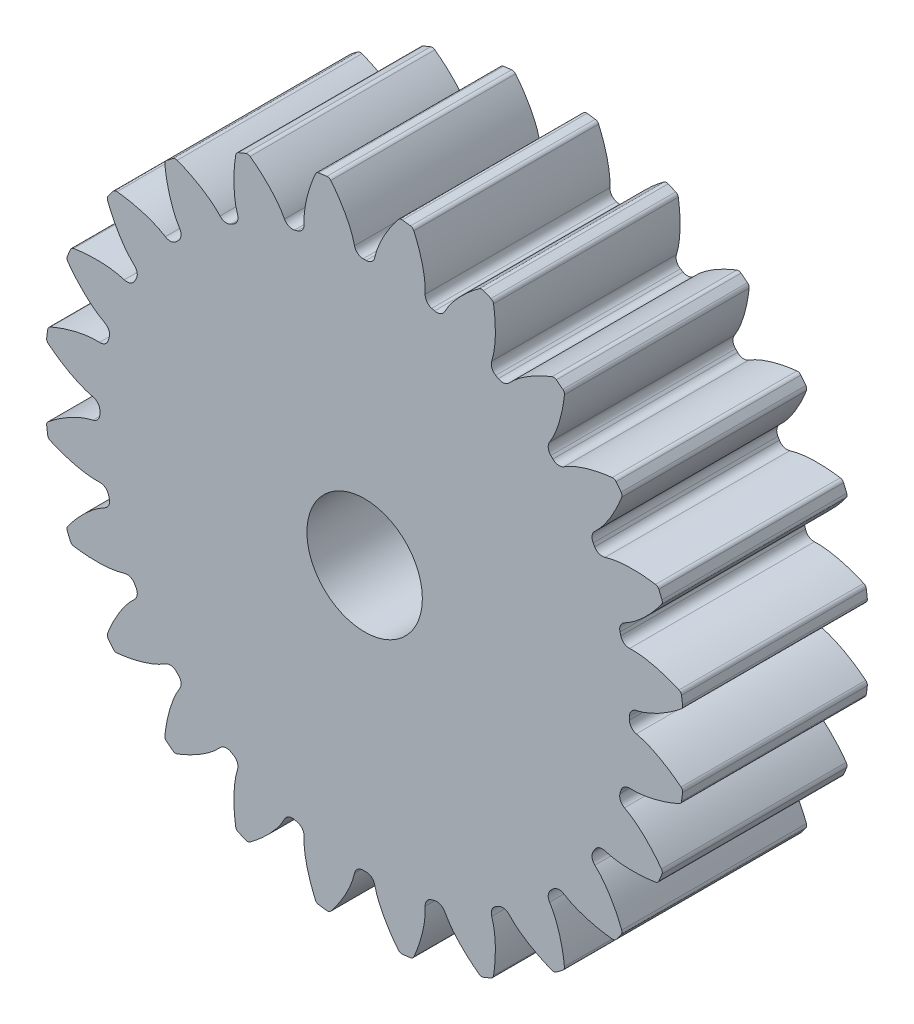
SolidWorks part; units mm, degrees
material "DELRIN"
ref_plane "Front" through (0, 0, 0) normal (0, 0, 1) x (1, 0, 0)
ref_plane "Top" through (0, 0, 0) normal (0, 1, 0) x (1, 0, 0)
ref_plane "Right" through (0, 0, 0) normal (1, 0, 0) x (0, 0, -1)
sketch "Sketch1" plane through (0, 0, 0) normal (0, 0, 1) x (1, 0, 0)
  circle A0 centre (0, 0) radius 22.0133
  dimension "OutsideDiameter" = 44.0267
extrude "Boss-Extrude1" add sketch "Sketch1" along normal blind 12.7
sketch "Sketch3" plane through (0, 0, 0) normal (0, 0, 1) x (1, 0, 0)
  line L0 (0, 0) -> (43.7181, 0) construction
  line L2 (0, 0) -> (-0.6456, 18.1919) construction
  line L3 (0, 0) -> (0.6456, 18.1919) construction
  line L4 (0.6456, 18.1919) -> (0.6532, 18.4046) construction
  line L5 (0, 0) -> (0, 61.276) construction
  line L6 (-0.6456, 18.1919) -> (-0.6532, 18.4046) construction
  circle A0 centre (0, 0) radius 22.0133 construction
  circle A1 centre (0, 0) radius 20.32 construction
  circle A2 centre (0, 0) radius 18.4162 construction
  arc A3 (0.6456, 18.1919) -> (-0.6456, 18.1919) centre (0, 0) ccw construction
  arc A5 (2.4284, 21.879) -> (-2.4284, 21.879) centre (0, 0) ccw
  spline S0 degree 4 poles (-0.6532, 18.4046) (-0.6535, 18.4104) (-0.6545, 18.4268) (-0.6575, 18.4576) (-0.6638, 18.5078) (-0.6738, 18.5716) (-0.6892, 18.6539) (-0.7103, 18.7504) (-0.7366, 18.856) (-0.7687, 18.9703) (-0.8037, 19.0839) (-0.8414, 19.1967) (-0.8815, 19.3085) (-0.9329, 19.4434) (-0.9987, 19.6042) (-1.0815, 19.7907) (-1.1824, 20.0005) (-1.2926, 20.2122) (-1.4071, 20.4189) (-1.5297, 20.6255) (-1.6532, 20.8239) (-1.7884, 21.0275) (-1.9168, 21.2143) (-2.0682, 21.4208) (-2.1926, 21.5866) (-2.3648, 21.8022) (-2.4689, 21.9286) (-2.5935, 22.0754) (-2.6502, 22.14) (-2.6851, 22.1798) knots 0 0 0 0 0 0.005377 0.015084 0.028532 0.04661 0.064855 0.092111 0.119476 0.146842 0.174209 0.201575 0.228941 0.256307 0.307035 0.361767 0.4165 0.471232 0.525964 0.580697 0.635429 0.690161 0.744894 0.799626 0.854358 0.909091 0.954545 1 1 1 1 1 construction
  spline S1 degree 4 poles (-0.6532, 18.4046) (-0.6535, 18.4104) (-0.6545, 18.4268) (-0.6575, 18.4576) (-0.6638, 18.5078) (-0.6738, 18.5716) (-0.6892, 18.6539) (-0.7103, 18.7504) (-0.7366, 18.856) (-0.7687, 18.9703) (-0.8037, 19.0839) (-0.8414, 19.1967) (-0.8815, 19.3085) (-0.9329, 19.4434) (-0.9987, 19.6042) (-1.0815, 19.7907) (-1.1824, 20.0005) (-1.2926, 20.2122) (-1.4071, 20.4189) (-1.5297, 20.6255) (-1.6532, 20.8239) (-1.7884, 21.0275) (-1.9168, 21.2143) (-2.0682, 21.4208) (-2.1926, 21.5866) (-2.3275, 21.7555) (-2.394, 21.8373) (-2.4284, 21.879) knots 0 0 0 0 0 0.005377 0.015084 0.028532 0.04661 0.064855 0.092111 0.119476 0.146842 0.174209 0.201575 0.228941 0.256307 0.307035 0.361767 0.4165 0.471232 0.525964 0.580697 0.635429 0.690161 0.744894 0.799626 0.854358 0.909091 0.909091 0.909091 0.909091 0.909091
  spline S2 degree 4 poles (0.6532, 18.4046) (0.6535, 18.4104) (0.6545, 18.4268) (0.6575, 18.4576) (0.6638, 18.5078) (0.6738, 18.5716) (0.6892, 18.6539) (0.7103, 18.7504) (0.7366, 18.856) (0.7687, 18.9703) (0.8037, 19.0839) (0.8414, 19.1967) (0.8815, 19.3085) (0.9329, 19.4434) (0.9987, 19.6042) (1.0815, 19.7907) (1.1824, 20.0005) (1.2926, 20.2122) (1.4071, 20.4189) (1.5297, 20.6255) (1.6532, 20.8239) (1.7884, 21.0275) (1.9168, 21.2143) (2.0682, 21.4208) (2.1926, 21.5866) (2.3648, 21.8022) (2.4689, 21.9286) (2.5935, 22.0754) (2.6502, 22.14) (2.6851, 22.1798) knots 0 0 0 0 0 0.005377 0.015084 0.028532 0.04661 0.064855 0.092111 0.119476 0.146842 0.174209 0.201575 0.228941 0.256307 0.307035 0.361767 0.4165 0.471232 0.525964 0.580697 0.635429 0.690161 0.744894 0.799626 0.854358 0.909091 0.954545 1 1 1 1 1 construction
  spline S3 degree 4 poles (0.6532, 18.4046) (0.6535, 18.4104) (0.6545, 18.4268) (0.6575, 18.4576) (0.6638, 18.5078) (0.6738, 18.5716) (0.6892, 18.6539) (0.7103, 18.7504) (0.7366, 18.856) (0.7687, 18.9703) (0.8037, 19.0839) (0.8414, 19.1967) (0.8815, 19.3085) (0.9329, 19.4434) (0.9987, 19.6042) (1.0815, 19.7907) (1.1824, 20.0005) (1.2926, 20.2122) (1.4071, 20.4189) (1.5297, 20.6255) (1.6532, 20.8239) (1.7884, 21.0275) (1.9168, 21.2143) (2.0682, 21.4208) (2.1926, 21.5866) (2.3275, 21.7555) (2.394, 21.8373) (2.4284, 21.879) knots 0 0 0 0 0 0.005377 0.015084 0.028532 0.04661 0.064855 0.092111 0.119476 0.146842 0.174209 0.201575 0.228941 0.256307 0.307035 0.361767 0.4165 0.471232 0.525964 0.580697 0.635429 0.690161 0.744894 0.799626 0.854358 0.909091 0.909091 0.909091 0.909091 0.909091
  point P0 (0, 18.2033)
  dimension "OutsideDiameter" = 44.0267
  dimension "PitchCircle" = 40.64
  dimension "BaseCircle" = 36.8323
  dimension "DedendumCircle" = 36.4067
sketch "DCLTBC" plane through (0, 0, 0) normal (0, 0, 1) x (1, 0, 0)
  line L0 (0, 0) -> (41.04, 0) construction
  line L1 (-0.6456, 18.1919) -> (-0.6532, 18.4046) construction
  line L2 (0.6456, 18.1919) -> (0.6532, 18.4046) construction
  line L3 (-0.6456, 18.1919) -> (-0.6532, 18.4046)
  line L4 (0.6456, 18.1919) -> (0.6532, 18.4046)
  line L5 (0, 0) -> (0, 104.9356) construction
  circle A0 centre (0, 0) radius 22.0133
  circle A1 centre (0, 0) radius 20.32 construction
  circle A2 centre (0, 0) radius 18.4162 construction
  arc A3 (0.6456, 18.1919) -> (-0.6456, 18.1919) centre (0, 0) ccw construction
  arc A4 (0.6456, 18.1919) -> (-0.6456, 18.1919) centre (0, 0) ccw
  spline S0 degree 4 poles (-999.1981, -34.6963) (-14.3386, 16.1827) (-0.8334, 17.2583) (-0.5869, 17.8923) (-0.6638, 18.5078) (-0.6738, 18.5716) (-0.6892, 18.6539) (-0.7103, 18.7504) (-0.7366, 18.856) (-0.7687, 18.9703) (-0.8037, 19.0839) (-0.8414, 19.1967) (-0.8815, 19.3085) (-0.9329, 19.4434) (-0.9987, 19.6042) (-1.0815, 19.7907) (-1.1824, 20.0005) (-1.2926, 20.2122) (-1.4071, 20.4189) (-1.5297, 20.6255) (-1.6532, 20.8239) (-1.7884, 21.0275) (-1.9168, 21.2143) (-2.0682, 21.4208) (-2.6456, 22.1903) (-4.6145, 24.4426) (15.9918, -0.7638) (-639.5408, 792.6401) knots -0.524597 -0.524597 -0.524597 -0.524597 -0.524597 0.005377 0.015084 0.028532 0.04661 0.064855 0.092111 0.119476 0.146842 0.174209 0.201575 0.228941 0.256307 0.307035 0.361767 0.4165 0.471232 0.525964 0.580697 0.635429 0.690161 0.744894 0.799626 0.854358 1.706051 1.706051 1.706051 1.706051 1.706051 only from (-0.6532, 18.4046) to (-2.4284, 21.879) construction
  spline S1 degree 4 poles (999.1981, -34.6963) (14.3386, 16.1827) (0.8334, 17.2583) (0.5869, 17.8923) (0.6638, 18.5078) (0.6738, 18.5716) (0.6892, 18.6539) (0.7103, 18.7504) (0.7366, 18.856) (0.7687, 18.9703) (0.8037, 19.0839) (0.8414, 19.1967) (0.8815, 19.3085) (0.9329, 19.4434) (0.9987, 19.6042) (1.0815, 19.7907) (1.1824, 20.0005) (1.2926, 20.2122) (1.4071, 20.4189) (1.5297, 20.6255) (1.6532, 20.8239) (1.7884, 21.0275) (1.9168, 21.2143) (2.0682, 21.4208) (2.6456, 22.1903) (4.6145, 24.4426) (-15.9918, -0.7638) (639.5408, 792.6401) knots -0.524597 -0.524597 -0.524597 -0.524597 -0.524597 0.005377 0.015084 0.028532 0.04661 0.064855 0.092111 0.119476 0.146842 0.174209 0.201575 0.228941 0.256307 0.307035 0.361767 0.4165 0.471232 0.525964 0.580697 0.635429 0.690161 0.744894 0.799626 0.854358 1.706051 1.706051 1.706051 1.706051 1.706051 only from (0.6532, 18.4046) to (2.4284, 21.879) construction
  spline S2 degree 4 poles (-0.6532, 18.4046) (-0.6535, 18.4104) (-0.6545, 18.4268) (-0.6575, 18.4576) (-0.6638, 18.5078) (-0.6738, 18.5716) (-0.6892, 18.6539) (-0.7103, 18.7504) (-0.7366, 18.856) (-0.7687, 18.9703) (-0.8037, 19.0839) (-0.8414, 19.1967) (-0.8815, 19.3085) (-0.9329, 19.4434) (-0.9987, 19.6042) (-1.0815, 19.7907) (-1.1824, 20.0005) (-1.2926, 20.2122) (-1.4071, 20.4189) (-1.5297, 20.6255) (-1.6532, 20.8239) (-1.7884, 21.0275) (-1.9168, 21.2143) (-2.0682, 21.4208) (-2.1926, 21.5866) (-2.3275, 21.7555) (-2.394, 21.8373) (-2.4284, 21.879) knots 0 0 0 0 0 0.005377 0.015084 0.028532 0.04661 0.064855 0.092111 0.119476 0.146842 0.174209 0.201575 0.228941 0.256307 0.307035 0.361767 0.4165 0.471232 0.525964 0.580697 0.635429 0.690161 0.744894 0.799626 0.854358 0.909091 0.909091 0.909091 0.909091 0.909091
  spline S3 degree 4 poles (0.6532, 18.4046) (0.6535, 18.4104) (0.6545, 18.4268) (0.6575, 18.4576) (0.6638, 18.5078) (0.6738, 18.5716) (0.6892, 18.6539) (0.7103, 18.7504) (0.7366, 18.856) (0.7687, 18.9703) (0.8037, 19.0839) (0.8414, 19.1967) (0.8815, 19.3085) (0.9329, 19.4434) (0.9987, 19.6042) (1.0815, 19.7907) (1.1824, 20.0005) (1.2926, 20.2122) (1.4071, 20.4189) (1.5297, 20.6255) (1.6532, 20.8239) (1.7884, 21.0275) (1.9168, 21.2143) (2.0682, 21.4208) (2.1926, 21.5866) (2.3275, 21.7555) (2.394, 21.8373) (2.4284, 21.879) knots 0 0 0 0 0 0.005377 0.015084 0.028532 0.04661 0.064855 0.092111 0.119476 0.146842 0.174209 0.201575 0.228941 0.256307 0.307035 0.361767 0.4165 0.471232 0.525964 0.580697 0.635429 0.690161 0.744894 0.799626 0.854358 0.909091 0.909091 0.909091 0.909091 0.909091
  dimension "OutsideDiameter" = 44.0267
  dimension "PitchCircle" = 40.64
  dimension "BaseCircle" = 36.8323
extrude "Cut-Extrude-DCLTBC" cut sketch "DCLTBC" along normal through all contours L4 S3 A0 S2 L3 A4 region at (0, 20.5304, 0)
fillet "Fillet-Tip-DCLTBC" radius 0.3011 2 edges at (2.4284, 21.879, 6.35) (-2.4284, 21.879, 6.35)
fillet "Fillet-Root-DCLTBC" radius 0.6022 2 edges at (-0.6456, 18.1919, 6.35) (0.6456, 18.1919, 6.35)
pattern_circular "CirPattern-DCLTBC" count 24 over 360 about axis through (0, 0, 12.7) along (0, 0, 1) of "Cut-Extrude-DCLTBC", "Fillet-Tip-DCLTBC", "Fillet-Root-DCLTBC"
sketch "DCGTBC" [suppressed] plane through (0, 0, 0) normal (0, 0, 1) x (1, 0, 0)
  line L0 (0, 0) -> (41.04, 0) construction
  line L1 (-60.6226, 5.3038) -> (0, 0) construction
  line L2 (0, 0) -> (60.6226, 5.3038) construction
  line L3 (0, 0) -> (-16.5124, 0)
  line L5 (0, 0) -> (0, 104.9356) construction
  circle A0 centre (0, 0) radius 65.6167
  circle A1 centre (0, 0) radius 63.5 construction
  circle A2 centre (0, 0) radius 57.5505 construction
  arc A3 (-0.231, 60.8537) -> (0.231, 60.8537) centre (0, 0) ccw construction
  arc A11 (60.6226, 5.3038) -> (-60.6226, 5.3038) centre (0, 0) ccw
  spline S4 degree 4 poles (999.5281, 37.5164) (15.9379, 54.4029) (0.0707, 55.4419) (-0.2895, 56.6024) (-0.2066, 57.7767) (-0.1929, 57.9173) (-0.1708, 58.0988) (-0.1393, 58.3123) (-0.0988, 58.5468) (-0.0484, 58.8015) (0.0074, 59.0552) (0.0683, 59.3079) (0.1336, 59.5593) (0.2182, 59.8633) (0.3273, 60.227) (0.4659, 60.6511) (0.6363, 61.1305) (0.824, 61.6174) (1.0202, 62.0951) (1.2316, 62.5758) (1.4455, 63.0396) (1.6812, 63.5192) (1.9056, 63.9609) (2.1719, 64.4533) (3.0421, 66.0274) (5.6872, 70.2084) (-15.0429, 35.5301) (520.7458, 920.9699) knots -0.449335 -0.449335 -0.449335 -0.449335 -0.449335 0.005377 0.015084 0.028532 0.04661 0.064855 0.092111 0.119476 0.146842 0.174209 0.201575 0.228941 0.256307 0.307035 0.361767 0.4165 0.471232 0.525964 0.580697 0.635429 0.690161 0.744894 0.799626 0.854358 1.559054 1.559054 1.559054 1.559054 1.559054 only from (-0.2184, 57.5501) to (2.8092, 65.5565) construction
  spline S5 degree 4 poles (-999.5281, 37.5164) (-15.9379, 54.4029) (-0.0707, 55.4419) (0.2895, 56.6024) (0.2066, 57.7767) (0.1929, 57.9173) (0.1708, 58.0988) (0.1393, 58.3123) (0.0988, 58.5468) (0.0484, 58.8015) (-0.0074, 59.0552) (-0.0683, 59.3079) (-0.1336, 59.5593) (-0.2182, 59.8633) (-0.3273, 60.227) (-0.4659, 60.6511) (-0.6363, 61.1305) (-0.824, 61.6174) (-1.0202, 62.0951) (-1.2316, 62.5758) (-1.4455, 63.0396) (-1.6812, 63.5192) (-1.9056, 63.9609) (-2.1719, 64.4533) (-3.0421, 66.0274) (-5.6872, 70.2084) (15.0429, 35.5301) (-520.7458, 920.9699) knots -0.449335 -0.449335 -0.449335 -0.449335 -0.449335 0.005377 0.015084 0.028532 0.04661 0.064855 0.092111 0.119476 0.146842 0.174209 0.201575 0.228941 0.256307 0.307035 0.361767 0.4165 0.471232 0.525964 0.580697 0.635429 0.690161 0.744894 0.799626 0.854358 1.559054 1.559054 1.559054 1.559054 1.559054 only from (0.2184, 57.5501) to (-2.8092, 65.5565) construction
  spline S6 degree 4 poles (-0.2184, 57.5501) (-0.2183, 57.5629) (-0.2176, 57.5987) (-0.2144, 57.6663) (-0.2066, 57.7767) (-0.1929, 57.9173) (-0.1708, 58.0988) (-0.1393, 58.3123) (-0.0988, 58.5468) (-0.0484, 58.8015) (0.0074, 59.0552) (0.0683, 59.3079) (0.1336, 59.5593) (0.2182, 59.8633) (0.3273, 60.227) (0.4659, 60.6511) (0.6363, 61.1305) (0.824, 61.6174) (1.0202, 62.0951) (1.2316, 62.5758) (1.4455, 63.0396) (1.6812, 63.5192) (1.9056, 63.9609) (2.1719, 64.4533) (2.3911, 64.8499) (2.63, 65.2574) (2.7481, 65.4554) (2.8092, 65.5565) knots 0 0 0 0 0 0.005377 0.015084 0.028532 0.04661 0.064855 0.092111 0.119476 0.146842 0.174209 0.201575 0.228941 0.256307 0.307035 0.361767 0.4165 0.471232 0.525964 0.580697 0.635429 0.690161 0.744894 0.799626 0.854358 0.909091 0.909091 0.909091 0.909091 0.909091
  spline S7 degree 4 poles (0.2184, 57.5501) (0.2183, 57.5629) (0.2176, 57.5987) (0.2144, 57.6663) (0.2066, 57.7767) (0.1929, 57.9173) (0.1708, 58.0988) (0.1393, 58.3123) (0.0988, 58.5468) (0.0484, 58.8015) (-0.0074, 59.0552) (-0.0683, 59.3079) (-0.1336, 59.5593) (-0.2182, 59.8633) (-0.3273, 60.227) (-0.4659, 60.6511) (-0.6363, 61.1305) (-0.824, 61.6174) (-1.0202, 62.0951) (-1.2316, 62.5758) (-1.4455, 63.0396) (-1.6812, 63.5192) (-1.9056, 63.9609) (-2.1719, 64.4533) (-2.3911, 64.8499) (-2.63, 65.2574) (-2.7481, 65.4554) (-2.8092, 65.5565) knots 0 0 0 0 0 0.005377 0.015084 0.028532 0.04661 0.064855 0.092111 0.119476 0.146842 0.174209 0.201575 0.228941 0.256307 0.307035 0.361767 0.4165 0.471232 0.525964 0.580697 0.635429 0.690161 0.744894 0.799626 0.854358 0.909091 0.909091 0.909091 0.909091 0.909091
  dimension "D1" = 5
  dimension "D2" = 5
  dimension "OutsideDiameter" = 44.0267
  dimension "PitchCircle" = 40.64
  dimension "BaseCircle" = 36.8323
extrude "Cut-Extrude-DCGTBC" [suppressed] cut sketch "DCGTBC" along normal through all
fillet "Fillet-Tip-DCGTBC" [suppressed] radius 0.3011
pattern_circular "CirPattern-DCGTBC" [suppressed] count 24 over 360 of bodies 112
sketch "Sketch8" plane through (0, 0, 0) normal (0, 0, 1) x (1, 0, 0)
  line L0 (18.125, -4.6) -> (21.725, -4.6)
  circle A2 centre (19.925, -7) radius 3
  circle A3 centre (0, 0) radius 3.9688
  dimension "D1" = 6
  dimension "D2" = 7.9375
  dimension "D3" = 3.6
extrude "Cut-Extrude5" cut sketch "Sketch8" along normal blind 25.4 contours A3 region at (0, 0, 0)
equation "\"DiametralPitch\"= 15'Diametral Pitch"
equation "\"NumTeeth\"= 24'Number of Teeth"
equation "\"PressureAngle\"= 25deg'Pressure Angle"
equation "\"Addendum\"= 1 / \"DiametralPitch\"'Addendum"
equation "\"Dedendum\"= 1.25 / \"DiametralPitch\"'Dedendum"
equation "\"WorkingDepth\"= 2 / \"DiametralPitch\"'Working Depth - here for REF (Not used in building model)"
equation "\"WholeDepth\"= 2.25 / \"DiametralPitch\"'Whole Depth - here for REF (Not used in building model)"
equation "\"Clearance\"= .25 / \"DiametralPitch\"'Clearance"
equation "\"CircularPitch\"= pi / \"DiametralPitch\"'Circular Pitch - here for REF (Not used in building model)"
equation "\"PitchCircle\"= \"NumTeeth\" / \"DiametralPitch\"'Pitch Circle - or - Pitch Diameter"
equation "\"OutsideDiameter\"= ( \"NumTeeth\" + 2 ) / \"DiametralPitch\"'Outside Diameter"
equation "\"Fillet_Root\"= \"Clearance\" * cos ( \"PressureAngle\" ) * tan ( ( 90 + \"PressureAngle\" ) / 2 ) 'Fillet Root"
equation "\"AddendumCircle\"= \"PitchCircle\" + ( 2 * \"Addendum\" )'Addendum Circle - or - Addendum Diameter"
equation "\"DedendumCircle\"= \"PitchCircle\" - ( 2 * \"Dedendum\" )'Dedendum Circle - or - Dedendum Diameter"
equation "\"BaseCircle\"= \"PitchCircle\" * cos ( \"PressureAngle\" )'Base Circle - Base Diameter"
equation "\"PitchAngle\"= 360deg / \"NumTeeth\"'Pitch Angle"
equation "\"Alpha\"= sqr ( \"PitchCircle\" ^ 2 - \"BaseCircle\" ^ 2 ) / \"BaseCircle\" * 180 / PI - \"PressureAngle\"'Alpha - Used for Calculating Beta"
equation "\"Beta\"= ( \"PitchAngle\" / 4 - ( \"Alpha\" - 90 ) )'Beta - Used in definition of the parameters for the parametric equation driven curve"
equation "\"Gamma\"= ( \"PitchAngle\" / 4 - ( \"Alpha\" + 90 ) )'Gamma - Used in definition of the parameters for the parametric equation driven curve"
equation "\"Phi\"= sqr ( ( \"AddendumCircle\" / 2 ) ^ 2 - ( \"BaseCircle\" / 2 ) ^ 2 ) / ( \"BaseCircle\" / 2 )'Phi - Used in definition of the parameters for the parametric equation driven curve"
equation "\"DCGTBC\"= iif ( \"DedendumCircle\" > \"BaseCircle\" , \"unsuppressed\" , \"suppressed\" )'if Dedendum Circle IS GREATER THAN BaseCircle THEN UnsuppressORSuppress FEATURE"
equation "\"DCLTBC\"= iif ( \"DedendumCircle\" - .002 > \"BaseCircle\" , \"suppressed\" , \"unsuppressed\" )'if Dedendum Circle - .002 IS GREATER THAN BaseCircle THEN SuppressORUnsuppress FEATURE"
equation "\"Cut-Extrude-DCGTBC\"= iif ( \"DedendumCircle\" > \"BaseCircle\" , \"unsuppressed\" , \"suppressed\" )'if Dedendum Circle IS GREATER THAN BaseCircle THEN UnsuppressORSuppress FEATURE"
equation "\"Cut-Extrude-DCLTBC\"= iif ( \"DedendumCircle\" - .002 > \"BaseCircle\" , \"suppressed\" , \"unsuppressed\" )'if Dedendum Circle - .002 IS GREATER THAN BaseCircle THEN SuppressORUnsuppress FEATURE"
equation "\"CirPattern-DCGTBC\"= iif ( \"DedendumCircle\" > \"BaseCircle\" , \"unsuppressed\" , \"suppressed\" )'if Dedendum Circle IS GREATER THAN BaseCircle THEN UnsuppressORSuppress FEATURE"
equation "\"CirPattern-DCLTBC\"= iif ( \"DedendumCircle\" - .002 > \"BaseCircle\" , \"suppressed\" , \"unsuppressed\" )'if Dedendum Circle - .002 IS GREATER THAN BaseCircle THEN SuppressORUnsuppress FEATURE"
equation "\"Fillet-Tip-DCGTBC\"= iif ( \"DedendumCircle\" > \"BaseCircle\" , \"unsuppressed\" , \"suppressed\" )'if Dedendum Circle IS GREATER THAN BaseCircle THEN UnsuppressORSuppress FEATURE"
equation "\"Fillet-Tip-DCLTBC\"= iif ( \"DedendumCircle\" - .002 > \"BaseCircle\" , \"suppressed\" , \"unsuppressed\" )'if Dedendum Circle - .002 IS GREATER THAN BaseCircle THEN SuppressORUnsuppress FEATURE"
equation "\"Fillet-Root-DCLTBC\"= iif ( \"DedendumCircle\" - .002 > \"BaseCircle\" , \"suppressed\" , \"unsuppressed\" )'if Dedendum Circle - .002 IS GREATER THAN BaseCircle THEN SuppressORUnsuppress FEATURE"
equation "\"D1@CirPattern-DCGTBC\"= \"NumTeeth\"'Number of Teeth"
equation "\"D1@CirPattern-DCLTBC\"= \"NumTeeth\"'Number of Teeth"
equation "\"D1@Fillet-Tip-DCGTBC\"= \"Fillet_Root\" / 2 'Tip Rad For Large No of Teeth"
equation "\"D1@Fillet-Tip-DCLTBC\"=\"Fillet_Root\" / 2'Tip Rad For Small No of Teeth"
equation "\"D1@Fillet-Root-DCLTBC\"= \"Fillet_Root\"'Fillet Root"
